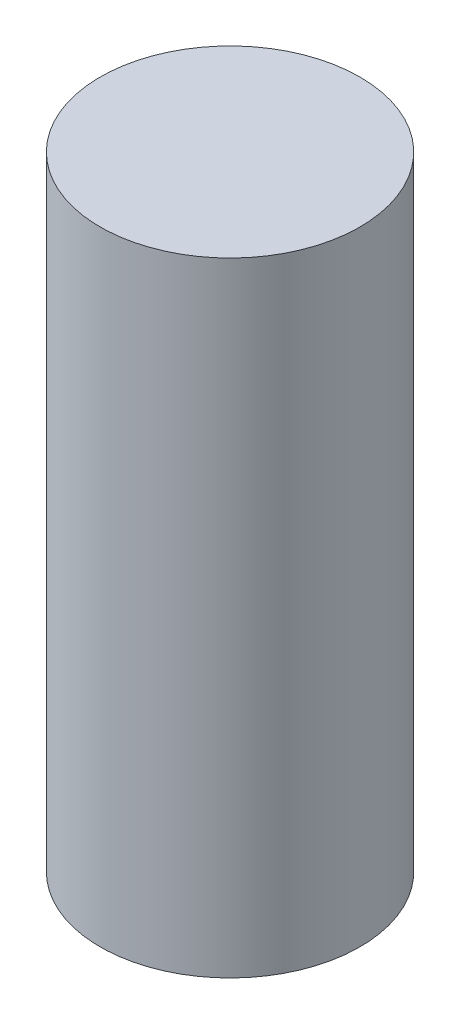
SolidWorks part; units mm, degrees
material "Silicon"
ref_plane "Front Plane" through (0, 0, 0) normal (0, 0, 1) x (1, 0, 0)
ref_plane "Top Plane" through (0, 0, 0) normal (0, 1, 0) x (1, 0, 0)
ref_plane "Right Plane" through (0, 0, 0) normal (1, 0, 0) x (0, 0, -1)
sketch "Main Parachute Bag Profile" plane through (0, 0, 0) normal (0, 1, 0) x (1, 0, 0)
  circle A0 centre (0, 0) radius 63.5
  dimension "D1" = 127
extrude "Main Parachute Bag Body" add sketch "Main Parachute Bag Profile" along normal blind 304.8 contours A0
equation "\"Packed Length\"= 12"
equation "\"Packed Diameter\"= 5"
equation "\"D1@Main Parachute Bag Body\"=\"Packed Length\""
